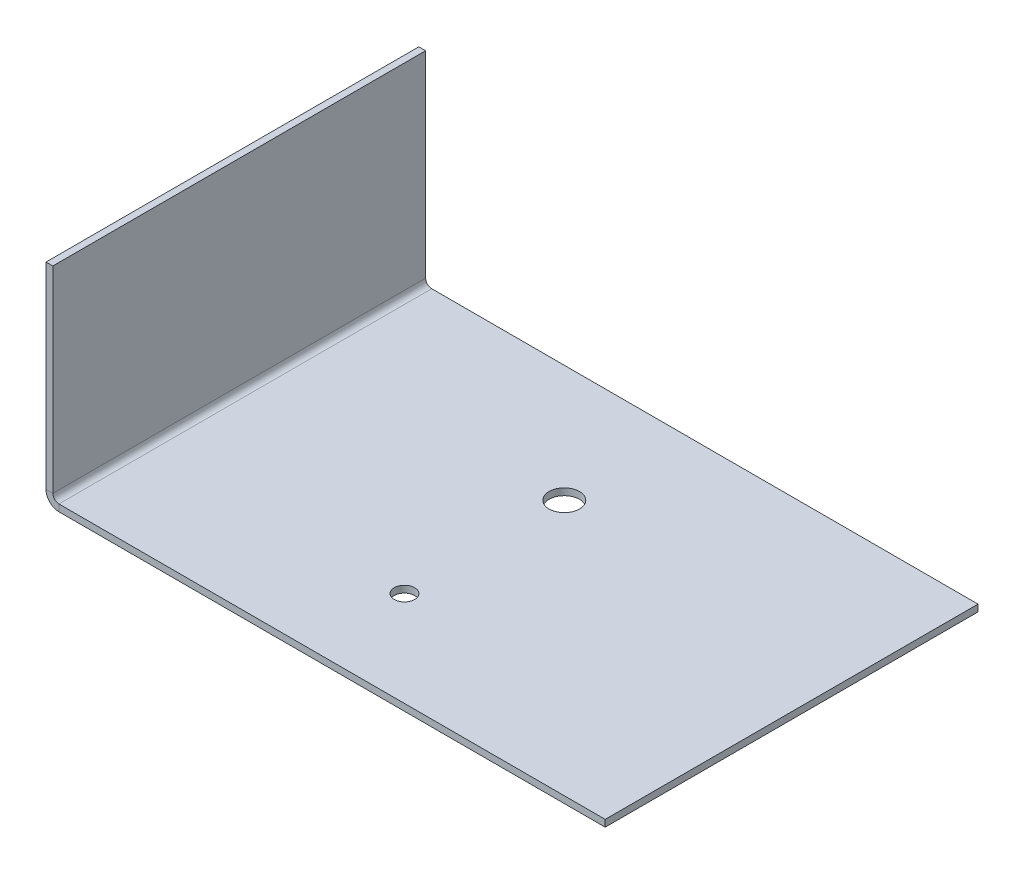
SolidWorks part; units mm, degrees
note: The reader was unsure of these and kept them because the rebuilt part matched: flange length of "Edge-Flange1".
material "Plain Carbon Steel"
ref_plane "Front Plane" through (0, 0, 0) normal (0, 0, 1) x (1, 0, 0)
ref_plane "Top Plane" through (0, 0, 0) normal (0, 1, 0) x (1, 0, 0)
ref_plane "Right Plane" through (0, 0, 0) normal (1, 0, 0) x (0, 0, -1)
sketch "Sketch1" plane through (0, 0, 0) normal (0, 1, 0) x (1, 0, 0)
  line L1 (0, 0) -> (152.4, 0)
  line L2 (0, 0) -> (0, 101.6)
  line L3 (0, 101.6) -> (152.4, 101.6)
  line L4 (152.4, 0) -> (152.4, 101.6)
  line L5 (0, 0) -> (152.4, 101.6) construction
  line L6 (0, 101.6) -> (152.4, 0) construction
  point P4 (76.2, 50.8)
  dimension "D1" = 101.6
  dimension "6" = 152.4
base flange "Base-Flange1" sketch "Sketch1" thickness 1.8542 reverse thickness direction no parameters "D1"=1.6637
edge flange "Edge-Flange1" sketch "Sketch8" flange angle 90 flange length 57.1881 flange position material inside bend radius 1.6637 thickness 1.8542 relief rectangular parameters "D6"=10
sketch "Sketch8" plane through (0, 0, 0) normal (-1, 0, 0) x (0, 0, 1)
  line L0 (-101.6, 0) -> (0, 0) construction
  line L1 (-101.6, 0) -> (0, 0)
  line L2 (-101.6, 0) -> (-101.6, 55.3339)
  line L3 (-101.6, 55.3339) -> (0, 55.3339)
  line L4 (0, 55.3339) -> (0, 0)
bend "EdgeBend1" bend radius 1.6637 bend angle 90 parameters "D5"=1
sketch "Sketch14" plane through (0, 0, 0) normal (0, 1, 0) x (1, 0, 0)
  circle A0 centre (71.7639, 25.9278) radius 2.7813
  dimension "D1" = 5.5626
extrude "TAP 1/4-20 Hole1" cut sketch "Sketch14" against normal blind 2.54 normal cut yes
sketch "Sketch15" plane through (0, 0, 0) normal (0, 1, 0) x (1, 0, 0)
  circle A0 centre (71.5155, 69.7385) radius 4.1414
extrude "TAPPED 3/8-16 Hole2" cut sketch "Sketch15" against normal blind 2.54
sketch "Bend-Lines1" [suppressed] plane through (0, 0, 0) normal (0, 1, 0) x (1, 0, 0)
sketch "Bounding-Box1" [suppressed] plane through (0, 0, 0) normal (0, 1, 0) x (1, 0, 0)
sheet metal parameters "Sheet-Metal6" thickness 1.8542 parameters "D1"=1.6637
flat pattern "Flat-Pattern6" [suppressed]
sketch "Bend-Lines2" plane through (0, 0, 0) normal (0, 1, 0) x (1, 0, 0)
sketch "Bounding-Box2" [suppressed] plane through (0, 0, 0) normal (0, 1, 0) x (1, 0, 0)
sheet metal parameters "Sheet-Metal7" thickness 1.8542 parameters "D1"=1.6637
flat pattern "Flat-Pattern6" [suppressed]
sketch "Bend-Lines2" plane through (0, 0, 0) normal (0, 1, 0) x (1, 0, 0)
sketch "Bounding-Box2" [suppressed] plane through (0, 0, 0) normal (0, 1, 0) x (1, 0, 0)
bend of the flat pattern "Flatten-<EdgeBend1>1"
sheet metal parameters "Sheet-Metal11" thickness 1.8542 parameters "D1"=1.6637
flat pattern "Flat-Pattern6"
sketch "Bend-Lines2" plane through (0, 0, 0) normal (0, 1, 0) x (1, 0, 0)
  line L0 (1.6628, 101.6) -> (1.6628, 0) construction
  line L1 (1.6628, 101.6) -> (1.6628, 0) construction
sketch3d "Bounding-Box2" [suppressed]
  line L0 (152.4, 101.6, 0) -> (-53.8625, 101.6, 0) construction
  line L1 (152.4, 0, 0) -> (-53.8625, 0, 0) construction
  line L2 (152.4, 101.6, 0) -> (152.4, 0, 0) construction
  line L3 (-53.8625, 101.6, 0) -> (-53.8625, 0, 0) construction
bend of the flat pattern "Flatten-<EdgeBend1>1"
sheet metal parameters "Sheet-Metal12" thickness 1.8542 parameters "D1"=1.6637
flat pattern "Flat-Pattern6"
sketch "Bend-Lines2" plane through (0, 0, 0) normal (0, 1, 0) x (1, 0, 0)
  line L0 (1.6628, 101.6) -> (1.6628, 0) construction
  line L1 (1.6628, 101.6) -> (1.6628, 0) construction
sketch3d "Bounding-Box2" [suppressed]
  line L0 (152.4, 101.6, 0) -> (-53.8625, 101.6, 0) construction
  line L1 (152.4, 0, 0) -> (-53.8625, 0, 0) construction
  line L2 (152.4, 101.6, 0) -> (152.4, 0, 0) construction
  line L3 (-53.8625, 101.6, 0) -> (-53.8625, 0, 0) construction
bend of the flat pattern "Flatten-<EdgeBend1>1"
